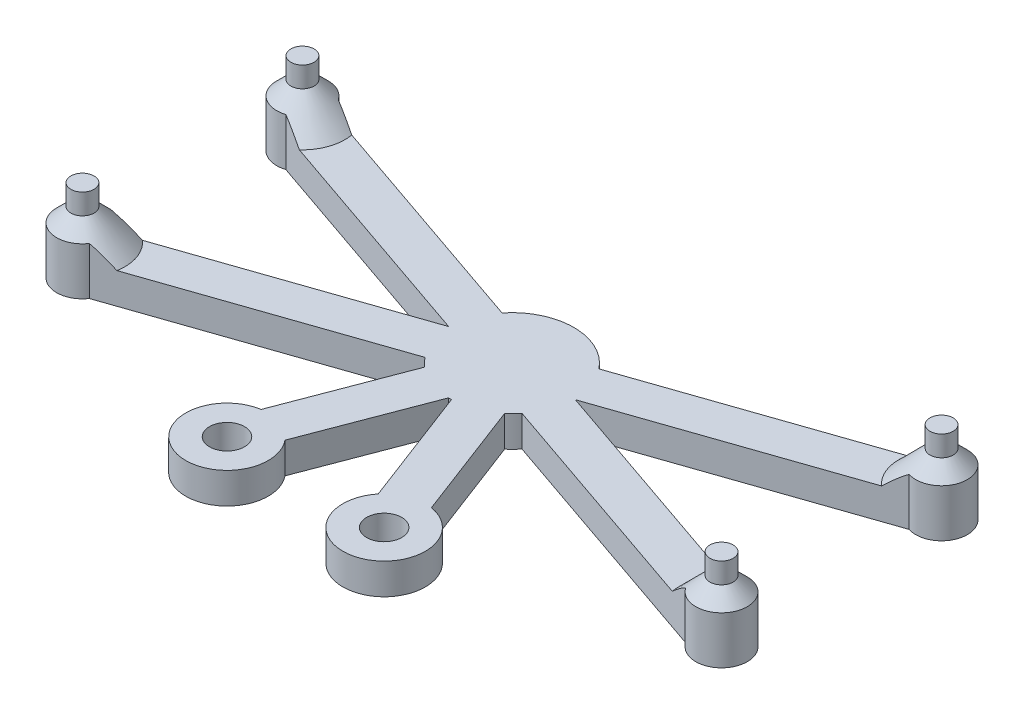
SolidWorks part; units mm, degrees
ref_plane "Front Plane" through (0, 0, 0) normal (0, 0, 1) x (1, 0, 0)
ref_plane "Top Plane" through (0, 0, 0) normal (0, 1, 0) x (1, 0, 0)
ref_plane "Right Plane" through (0, 0, 0) normal (1, 0, 0) x (0, 0, -1)
sketch "Sketch1" plane through (0, 0, 0) normal (0, 1, 0) x (1, 0, 0)
  line L0 (-30.9695, -12.7185) -> (31.0065, -12.7185) construction
  line L1 (33.0385, -10.6865) -> (33.0385, 10.6495) construction
  line L2 (31.0065, 12.6815) -> (-31.0965, 12.6815) construction
  line L3 (-33.0015, 10.7765) -> (-33.0015, -10.6865) construction
  line L4 (-30.9695, 10.6495) -> (31.0065, -10.6865) construction
  line L5 (31.0065, 10.6495) -> (-30.9695, -10.6865) construction
  line L6 (-30.2022, 8.2702) -> (-6.1256, -0.0185)
  line L7 (28.9372, 12.0523) -> (4.7162, 3.714)
  line L8 (-28.9002, 12.0523) -> (-4.6792, 3.714)
  line L9 (30.2392, 8.2702) -> (6.1626, -0.0185)
  line L10 (-30.3185, 12.5406) -> (31.6575, -8.7954) construction
  line L11 (-31.6205, 8.7584) -> (30.3555, -12.5776) construction
  line L12 (-6.1256, -0.0185) -> (-30.2033, -8.3075)
  line L13 (30.3555, 12.5406) -> (-31.6205, -8.7954) construction
  line L14 (6.1626, -0.0185) -> (30.2403, -8.3075)
  line L15 (-4.6792, -3.751) -> (-28.9004, -12.0894)
  line L16 (31.6575, 8.7584) -> (-30.3185, -12.5776) construction
  line L17 (4.7162, -3.751) -> (28.9374, -12.0894)
  arc A0 (31.0065, -12.7185) -> (33.0385, -10.6865) centre (31.007, -10.687) ccw construction
  arc A1 (33.0385, 10.6495) -> (31.0065, 12.6815) centre (31.007, 10.65) ccw construction
  arc A2 (-31.0965, 12.6815) -> (-33.0015, 10.7765) centre (-31.0964, 10.7764) ccw construction
  arc A3 (-33.0015, -10.6865) -> (-30.9695, -12.7185) centre (-30.97, -10.687) ccw construction
  circle A4 centre (-30.9695, 10.6495) radius 1.125
  circle A5 centre (-30.9695, -10.6865) radius 1.125
  circle A6 centre (31.0065, -10.6865) radius 1.125
  circle A7 centre (31.0065, 10.6495) radius 1.125
  circle A8 centre (-30.9695, 10.6495) radius 1.125
  arc A9 (-28.9002, 12.0523) -> (-30.2022, 8.2702) centre (-30.9695, 10.6495) ccw
  arc A10 (30.2392, 8.2702) -> (28.9372, 12.0523) centre (31.0065, 10.6495) ccw
  arc A11 (28.9374, -12.0894) -> (30.2403, -8.3075) centre (31.007, -10.687) ccw
  arc A12 (-30.2033, -8.3075) -> (-28.9004, -12.0894) centre (-30.97, -10.687) ccw
  arc A13 (4.7162, 3.714) -> (-4.6792, 3.714) centre (0.0185, -0.0185) ccw
  arc A14 (-4.6792, -3.751) -> (4.7162, -3.751) centre (0.0185, -0.0185) ccw
  point P34 (0, 0)
  dimension "D3" = 5
  dimension "D4" = 5
  dimension "D5" = 5
  dimension "D6" = 5
  dimension "D7" = 12
  dimension "D1" = 2
  dimension "D2" = 2
extrude "Boss-Extrude1" add sketch "Sketch1" along normal blind 3 contours L6 L12 A12 L15 A14 L17 A11 L14 L9 A10 L7 A13 L8 A9
sketch "Sketch2" plane through (0, 3, 0) normal (0, 1, 0) x (1, 0, 0)
  circle A0 centre (31.0065, 10.6495) radius 1.125 construction
  circle A1 centre (31.0065, -10.6865) radius 1.125 construction
  circle A2 centre (-30.9695, -10.6865) radius 1.125 construction
  circle A3 centre (-30.9695, 10.6495) radius 1.125 construction
  circle A4 centre (31.0065, 10.6495) radius 1.125
  circle A5 centre (31.0065, -10.6865) radius 1.125
  circle A6 centre (-30.9695, -10.6865) radius 1.125
  circle A7 centre (-30.9695, 10.6495) radius 1.125
extrude "Boss-Extrude2" add sketch "Sketch2" along normal blind 5 contours A6 | A5 | A4 | A7 region at (31.0065, 3, -10.6495) region at (31.0065, 3, 10.6865) region at (-30.9695, 3, 10.6865)
chamfer "Chamfer1" distance 3 angle 45 4 edges at (31.0065, 3, -9.5245) (31.0065, 3, 11.8115) (-30.9695, 3, 11.8115) (-30.9695, 3, -9.5245)
sketch "Sketch4" plane through (0, 3, 0) normal (0, 1, 0) x (1, 0, 0)
  line L0 (-6.1256, -0.0185) -> (6.1626, -0.0185)
  line L2 (0, 5.9815) -> (0, -6.0185)
  arc A0 (-4.6792, -3.751) -> (4.7162, -3.751) centre (0.0185, -0.0185) ccw construction
  arc A1 (4.7162, 3.714) -> (-4.6792, 3.714) centre (0.0185, -0.0185) ccw construction
  arc A2 (-4.6792, -3.751) -> (4.7162, -3.751) centre (0.0185, -0.0185) ccw
  arc A3 (4.7162, 3.714) -> (-4.6792, 3.714) centre (0.0185, -0.0185) ccw
sketch "Sketch5" plane through (0, 3, 0) normal (0, 1, 0) x (1, 0, 0)
  line L0 (-7.62, -20.0185) -> (0, -0.0185) construction
  line L1 (7.62, -20.0185) -> (0, -0.0185) construction
  line L2 (-4.5177, -17.4935) -> (-0.1449, -6.0163)
  line L3 (4.5177, -17.4935) -> (0.1452, -6.0172)
  line L4 (-8.2556, -16.0693) -> (-3.8784, -4.5807)
  line L5 (8.2556, -16.0693) -> (3.8875, -4.6044)
  line L6 (-9.4889, -19.3064) -> (0, 5.5989) construction
  line L7 (9.4889, -19.3064) -> (0, 5.5989) construction
  line L8 (-5.7511, -20.7306) -> (0, -5.6359) construction
  line L9 (5.7511, -20.7306) -> (0, -5.6359) construction
  circle A0 centre (-7.62, -20.0185) radius 1.7
  circle A1 centre (7.62, -20.0185) radius 1.7
  arc A2 (-8.2556, -16.0693) -> (-4.5177, -17.4935) centre (-7.62, -20.0185) ccw
  arc A3 (4.5177, -17.4935) -> (8.2556, -16.0693) centre (7.62, -20.0185) ccw
  arc A4 (-4.6792, -3.751) -> (4.7162, -3.751) centre (0.0185, -0.0185) ccw construction
  arc A6 (-0.1449, -6.0163) -> (0.1452, -6.0172) centre (0.0185, -0.0185) ccw
  arc A8 (-3.8784, -4.5807) -> (3.8875, -4.6044) centre (0.0185, -0.0185) ccw
  arc M13 (-4.6792, -3.751) -> (4.7162, -3.751) centre (0.0185, -0.0185) ccw
  dimension "D1" = 2
  dimension "D2" = 2
extrude "Boss-Extrude3" add sketch "Sketch5" against normal through all contours L4 A2 L2 A0 M13 | L3 A3 L5 A1 M13 region at (-5.7885, 3, 15.211) region at (5.7904, 3, 15.217)
